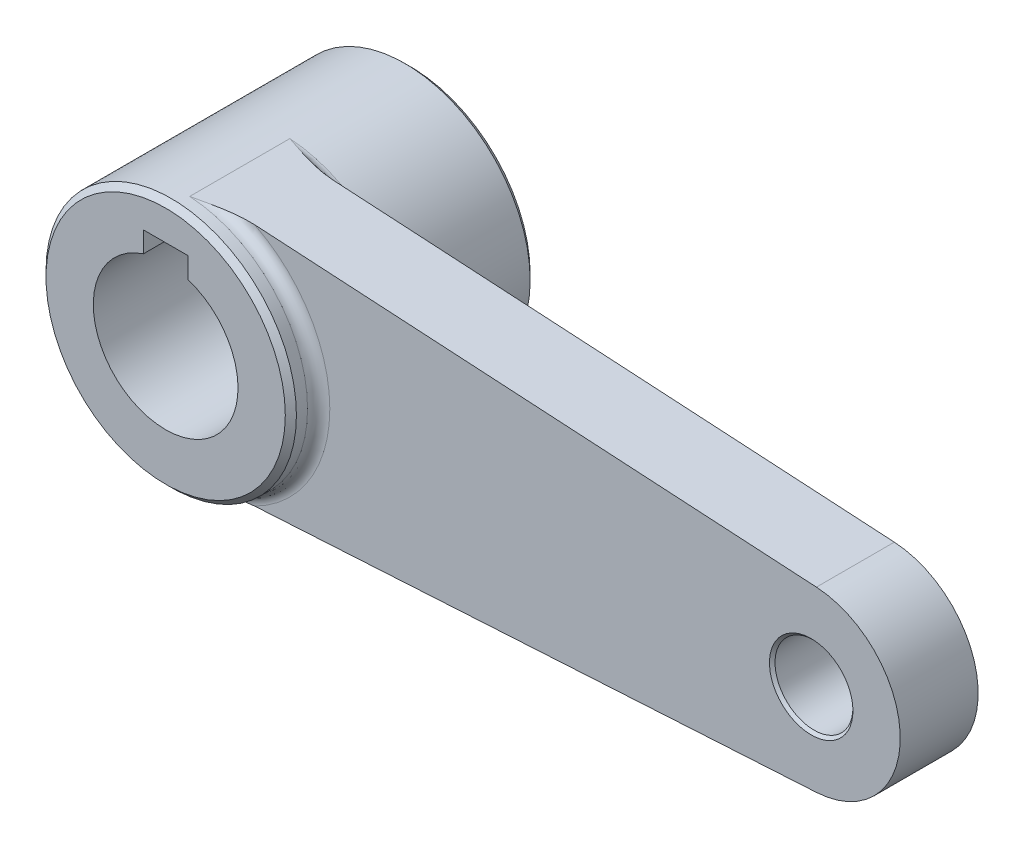
SolidWorks part; units mm, degrees
material "Простая углеродистая сталь"
ref_plane "Спереди" through (0, 0, 0) normal (0, 0, 1) x (1, 0, 0)
ref_plane "Сверху" through (0, 0, 0) normal (0, 1, 0) x (1, 0, 0)
ref_plane "Справа" through (0, 0, 0) normal (1, 0, 0) x (0, 0, -1)
sketch "Эскиз1" plane through (0, 0, 0) normal (0, 0, 1) x (1, 0, 0)
  line L0 (0, 0) -> (111, 0) construction
  line L7 (1.3176, 22.4614) -> (111.9369, 15.9725)
  line L8 (1.3176, -22.4614) -> (111.9369, -15.9725)
  circle A0 centre (0, 0) radius 22.5
  circle A2 centre (111, 0) radius 16
  circle A3 centre (111, 0) radius 7
  dimension "D5" = 45
  dimension "D6" = 16
  dimension "D7" = 14
  dimension "D1" = 111
extrude "Бобышка-Вытянуть1" add sketch "Эскиз1" along normal mid plane 14 contours A2 L7 A0 L8 | A2 A3 | A0 | L0 A0 L8 A2 region at (56.6629, 10.1642, 0) region at (15.9061, -15.0004, 0) region at (56.6629, -10.1642, 0) region at (100.333, 11.311, 0)
extrude "Бобышка-Вытянуть2" add sketch "Эскиз1<3>" along normal offset from surface (12 mm away) 5 contours A0 region at (0, 0, 0) up to face at (54.4386, 0, 7) offset beyond the face yes
sketch "Эскиз1<3>" plane through (0, 0, 0) normal (0, 0, 1) x (1, 0, 0) same geometry as "Эскиз1"
extrude "Бобышка-Вытянуть3" add sketch "Эскиз1<5>" against normal offset from surface (32 mm away) 44 contours A0 region at (0, 0, 0) up to face at (22.5, 0, 12)
sketch "Эскиз1<5>" plane through (0, 0, 0) normal (0, 0, 1) x (1, 0, 0) same geometry as "Эскиз1"
fillet "Скругление1" radius 2 2 edges at (22.5, 0, -7) (22.5, 0, 7)
chamfer "Фаска1" distance 0.5 angle 45 2 edges at (118, 0, -7) (118, 0, 7)
chamfer "Фаска2" distance 1 angle 45 2 edges at (22.5, 0, -32) (22.5, 0, 12)
sketch "Эскиз2" plane through (0, 0, 12) normal (0, 0, 1) x (1, 0, 0)
  line L1 (4, 0) -> (-4, 0)
  line L2 (4, 0) -> (4, 16.1)
  line L3 (4, 16.1) -> (-4, 16.1)
  line L4 (-4, 0) -> (-4, 16.1)
  circle A0 centre (0, 0) radius 13
  point P3 (0, 3.2389)
  dimension "D1" = 26
  dimension "D2" = 29.1
  dimension "D3" = 8
extrude "Вырез-Вытянуть1" cut sketch "Эскиз2" against normal through all contours L4 A0 L2 L1 | L2 A0 L4 L1 | A0 L2 L3 L4 region at (0, -1.5275, 12) region at (0, 6.3973, 12) region at (0, 14.4406, 12)
